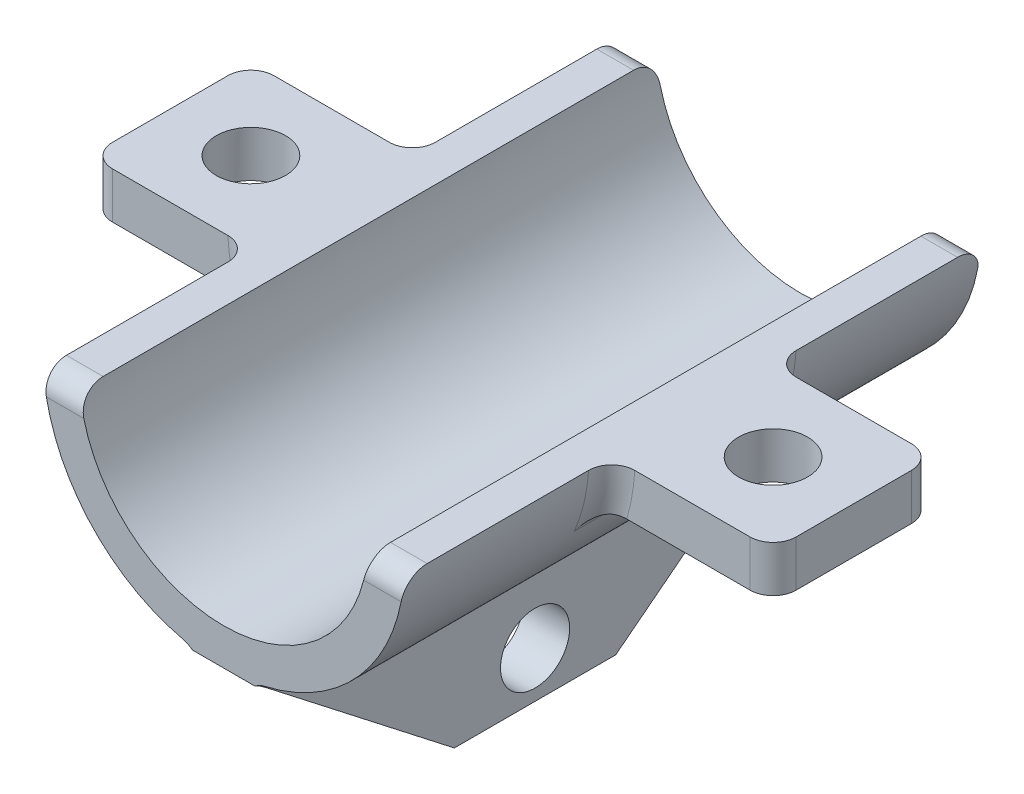
SolidWorks part; units mm, degrees
ref_plane "Front Plane" through (0, 0, 0) normal (0, 0, 1) x (1, 0, 0)
ref_plane "Top Plane" through (0, 0, 0) normal (0, 1, 0) x (1, 0, 0)
ref_plane "Right Plane" through (0, 0, 0) normal (1, 0, 0) x (0, 0, -1)
other "Bounding Box"
ref_plane "Default Plane" through (-14.8215, -0.5, -12.5) normal (0, 0, 1) x (1, 0, 0)
sketch "Sketch3" plane through (0, 0, 0) normal (0, 0, 1) x (1, 0, 0)
  line L0 (-7.8215, -0.5) -> (-6.23, -0.5)
  line L1 (6.23, -0.5) -> (7.8215, -0.5)
  arc A0 (-6.23, -0.5) -> (6.23, -0.5) centre (0, 0) ccw
  arc A1 (-7.8215, -0.5) -> (7.8215, -0.5) centre (0, 0) ccw
  dimension "D1" = 12.5
  dimension "D2" = 15.675
  dimension "D3" = 0.5
extrude "Boss-Extrude1" add sketch "Sketch3" along normal mid plane 25
sketch "Sketch6" plane through (0, 0, 0) normal (0, 1, 0) x (1, 0, 0)
  line L0 (14.8215, -12.3058) -> (14.8215, 12.5663) construction
  line L1 (7.8215, -12.5) -> (7.8215, 12.5) construction
  dimension "D1" = 7
ref_plane "Plane1" through (14.8215, 0, 0) normal (1, 0, 0) x (0, 0, -1)
sketch "Sketch7" plane through (14.8215, 0, 0) normal (1, 0, 0) x (0, 0, -1)
  line L0 (-12.5, -0.5) -> (12.5, -0.5) construction
  line L1 (-3.5, -0.5) -> (3.5, -0.5)
  line L2 (-3.5, -0.5) -> (-3.5, -2.5)
  line L3 (-3.5, -2.5) -> (3.5, -2.5)
  line L4 (3.5, -0.5) -> (3.5, -2.5)
  point P6 (0, -0.5)
  dimension "D1" = 7
  dimension "D2" = 2
extrude "Boss-Extrude8" add sketch "Sketch7" against normal up to surface (7 mm away) up to face at (0, -4.1688, 0)
sketch "Sketch8" plane through (0, -0.5, 0) normal (0, 1, 0) x (1, 0, 0)
  line L0 (7.8215, -3.5) -> (7.8215, 3.5) construction
  line L1 (7.8215, 3.5) -> (14.8215, -3.5) construction
  circle A0 centre (11.3215, 0) radius 1.5
  dimension "D1" = 3
extrude "Cut-Extrude1" cut sketch "Sketch8" against normal up to surface (2 mm away) up to face at (11.1248, -2.5, 0)
fillet "Fillet1" radius 1 5 edges at (7.6901, -1.5128, -3.5) (7.6901, -1.5128, 3.5) (7.4281, -2.5, 0) (14.8215, -1.5, -3.5) (14.8215, -1.5, 3.5)
mirror "Mirror1" about plane through (0, 0, 0) normal (1, 0, 0) of "Fillet1", "Cut-Extrude1", "Boss-Extrude8"
sketch "Sketch9" plane through (0, 0, 0) normal (1, 0, 0) x (0, 0, -1)
  line L5 (-12.5, -7.8375) -> (-3.5, -14.8375)
  line L6 (-3.5, -14.8375) -> (3.5, -14.8375)
  line L7 (3.5, -14.8375) -> (12.5, -7.8375)
  line L10 (-12.5, -7.8375) -> (-12.5, -6.25)
  line L11 (-12.5, -6.25) -> (12.5, -6.25)
  line L12 (12.5, -7.8375) -> (12.5, -0.5) construction
  line L13 (-12.5, -6.25) -> (12.5, -6.25) construction
  line L14 (12.5, -6.25) -> (12.5, -7.8375)
  line L15 (-12.5, -7.8375) -> (12.5, -7.8375) construction
  circle A0 centre (0, -12.8375) radius 1.5
  point P4 (0, -14.8375)
  point P24 (0, -6.25)
  dimension "D2" = 3
  dimension "D3" = 7
  dimension "D4" = 2
  dimension "D1" = 7
extrude "Boss-Extrude9" add sketch "Sketch9" along normal mid plane 2
fillet "Fillet2" radius 1 6 edges at (-1, -7.7734, 0) (1, -7.7734, 0) (7.0258, -0.5, 12.5) (7.0258, -0.5, -12.5) (-7.0258, -0.5, -12.5) (-7.0258, -0.5, 12.5)
